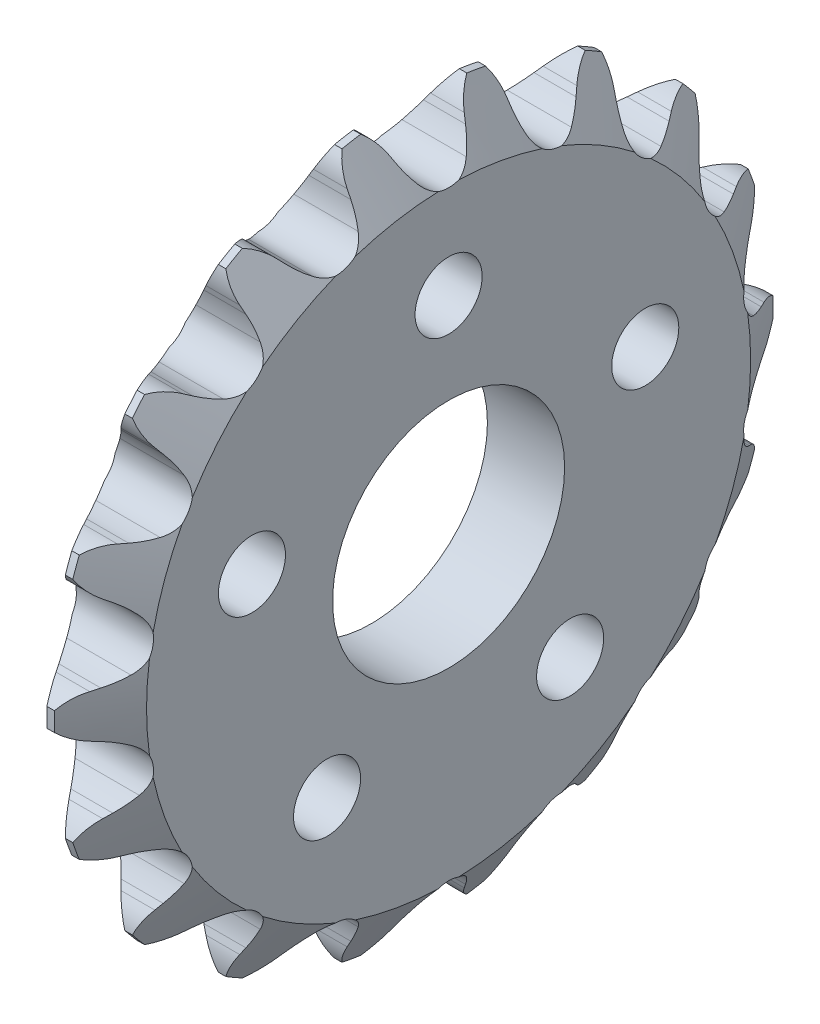
SolidWorks part; units mm, degrees
material "Alloy Steel"
ref_plane "Front Plane" through (0, 0, 0) normal (0, 0, 1) x (1, 0, 0)
ref_plane "Top Plane" through (0, 0, 0) normal (0, 1, 0) x (1, 0, 0)
ref_plane "Right Plane" through (0, 0, 0) normal (1, 0, 0) x (0, 0, -1)
ref_axis "X AXIS" through (-88.99, 0, 0) along (1, 0, 0)
ref_axis "Y AXIS" through (0, -55, 0) along (0, 1, 0)
ref_axis "Z AXIS" through (0, 0, 55) along (0, 0, -1)
other "Freeze***"
sketch "Sketch1" plane through (0, 0, 0) normal (1, 0, 0) x (0, 0, -1)
  line L0 (0, 18.2841) -> (-6.2535, 17.1814) construction
  line L1 (-1.9086, 18.1962) -> (-2.0662, 18.5596)
  line L2 (-1.9086, 18.1962) -> (2.0721, 19.9225) construction
  line L3 (2.0721, 19.9225) -> (0, 18.2841) construction
  line L4 (0, 18.2841) -> (-1.9468, 18.2841) construction
  line L5 (-3.5246, 19.9889) -> (-3.1268, 17.7328) construction
  line L6 (0, 18.2841) -> (0, 16.5867) construction
  circle A0 centre (0, 0) radius 18.2841 construction
  arc A1 (-1.3314, 17.2313) -> (0, 16.5867) centre (0, 18.2841) ccw
  arc A2 (-1.3314, 17.2313) -> (-1.9086, 18.1962) centre (2.0721, 19.9225) cw
  arc A3 (-2.0662, 18.5596) -> (-3.5246, 19.9889) centre (-4.5526, 17.4814) ccw
sketch "Sketch2" plane through (0, 0, 0) normal (0, 0, 1) x (1, 0, 0)
  line L0 (0, 0) -> (0, 19.8716) construction
  line L1 (-0.2064, 19.8716) -> (0.2064, 19.8716)
  line L2 (0.2064, 19.8716) -> (2.1336, 16.6966)
  line L3 (2.1336, 16.6966) -> (2.1336, 0)
  line L4 (-2.1336, 0) -> (2.1336, 0)
  line L5 (-2.1336, 16.6966) -> (-2.1336, 0)
  line L6 (-0.2064, 19.8716) -> (-2.1336, 16.6966)
  dimension "D1" = 19.8716
  dimension "D2" = 4.2672
revolve "Revolve1" add sketch "Sketch2" angle 360 about L4
sketch "Sketch3" plane through (0, 0, 0) normal (1, 0, 0) x (0, 0, -1)
  line L0 (-1.9086, 18.1962) -> (-2.0662, 18.5596) construction
  line L1 (-1.9086, 18.1962) -> (-2.0662, 18.5596)
  line L2 (0, 16.5867) -> (0, 0) construction
  line L3 (1.9086, 18.1962) -> (2.0662, 18.5596)
  arc A0 (-2.0662, 18.5596) -> (-3.5246, 19.9889) centre (-4.5526, 17.4814) ccw construction
  arc A1 (-1.9086, 18.1962) -> (-1.3314, 17.2313) centre (2.0721, 19.9225) ccw construction
  arc A2 (-1.3314, 17.2313) -> (0, 16.5867) centre (0, 18.2841) ccw construction
  arc A3 (-2.0662, 18.5596) -> (-3.5246, 19.9889) centre (-4.5526, 17.4814) ccw
  arc A4 (-1.9086, 18.1962) -> (-1.3314, 17.2313) centre (2.0721, 19.9225) ccw
  arc A5 (-1.3314, 17.2313) -> (1.3314, 17.2313) centre (0, 18.2841) ccw
  arc A6 (1.9086, 18.1962) -> (1.3314, 17.2313) centre (-2.0721, 19.9225) cw
  arc A7 (2.0662, 18.5596) -> (3.5246, 19.9889) centre (4.5526, 17.4814) cw
  arc A8 (-3.5246, 19.9889) -> (3.5246, 19.9889) centre (0, 0) cw
extrude "Cut-Extrude1" cut sketch "Sketch3" against normal through all both and the other way through all contours A8 A3 L1 A4 A5 A6 L3 A7 region at (0, 18.7821, 0)
pattern_circular "CirPattern1" count 18 over 360 about axis through (-88.99, 0, 0) along (1, 0, 0) of "Cut-Extrude1"
sketch "Sketch4" plane through (2.1336, 0, 0) normal (1, 0, 0) x (0, 0, -1)
  line L0 (0, 0) -> (0, 11.43) construction
  circle A0 centre (0, 0) radius 6.4135
  circle A1 centre (0, 11.43) radius 1.8542
  circle A2 centre (10.8706, 3.5321) radius 1.8542
  circle A3 centre (6.7184, -9.2471) radius 1.8542
  circle A4 centre (-6.7184, -9.2471) radius 1.8542
  circle A5 centre (-10.8706, 3.5321) radius 1.8542
  point P15 (0, 0)
  dimension "D1" = 12.827
  dimension "D2" = 5
  dimension "D3" = 3.7084
  dimension "D4" = 11.43
extrude "Cut-Extrude2" cut sketch "Sketch4" against normal through all
equation "\"p\"= 2 / 8"
equation "\"n\"= 18"
equation "\"Dr\"= 0.13"
equation "\"Ds\"= 1.005 * \"Dr\" + 0.003"
equation "\"PD\"= \"p\" * cosec ( 180 / \"n\" )"
equation "\"A\"= 35 + 60 / \"n\""
equation "\"B\"= 18 - 56 / \"n\""
equation "\"ac\"= 0.8 * \"Dr\""
equation "\"ab\"= 1.4 * \"Dr\""
equation "\"D1@Sketch1\"=\"PD\""
equation "\"D2@Sketch1\"=\"p\""
equation "\"D3@Sketch1\"=\"Ds\""
equation "\"D4@Sketch1\"=\"A\""
equation "\"D5@Sketch1\"=\"B\""
equation "\"D6@Sketch1\"=\"ac\""
equation "\"D7@Sketch1\"=\"ab\""
equation "\"D1@Sketch2\"=(\"PD\"+\"p\"/2)/2"
equation "\"D4@Sketch2\"=\"p\"/2"
equation "\"D1@CirPattern1\"=\"n\""
